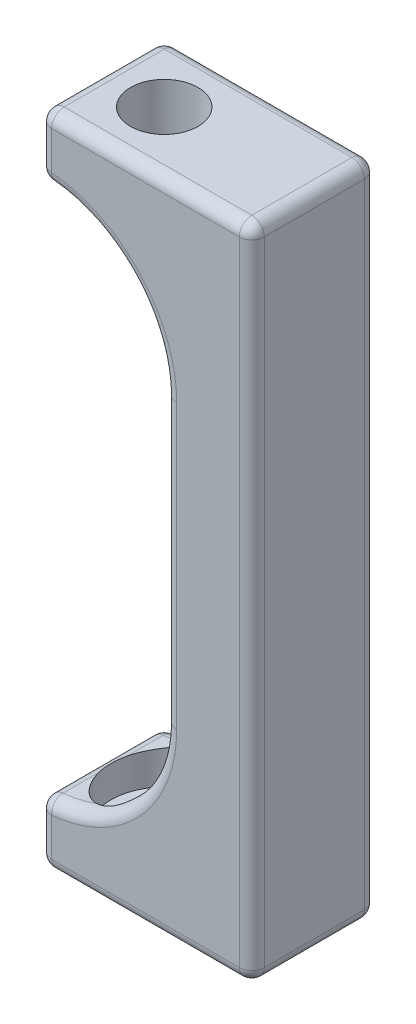
SolidWorks part; units mm, degrees
ref_plane "Front Plane" through (0, 0, 0) normal (0, 0, 1) x (1, 0, 0)
ref_plane "Top Plane" through (0, 0, 0) normal (0, 1, 0) x (1, 0, 0)
ref_plane "Right Plane" through (0, 0, 0) normal (1, 0, 0) x (0, 0, -1)
sketch "Sketch1" plane through (0, 0, 0) normal (0, 0, 1) x (1, 0, 0)
  line L0 (3.5, 0) -> (-32.6297, 0) construction
  line L1 (-3.5, -26.3) -> (3.5, -26.3)
  line L2 (-3.5, -26.3) -> (-3.5, 26.3)
  line L3 (-3.5, 26.3) -> (3.5, 26.3)
  line L4 (3.5, -26.3) -> (3.5, 26.3)
  line L5 (-3.5, -26.3) -> (3.5, 26.3) construction
  line L6 (-3.5, 26.3) -> (3.5, -26.3) construction
  line L7 (-3.5, 21.3) -> (-13.5, 21.3)
  line L8 (-3.5, -26.3) -> (-13.5, -26.3)
  line L9 (-3.5, -26.3) -> (-3.5, -21.3)
  line L10 (-3.5, -21.3) -> (-13.5, -21.3)
  line L11 (-13.5, -26.3) -> (-13.5, -21.3)
  line L12 (-13.5, 26.3) -> (-13.5, 21.3)
  line L13 (-3.5, 26.3) -> (-13.5, 26.3)
  point P0 (0, 0)
  dimension "D1" = 52.6
  dimension "D2" = 7
  dimension "D3" = 10
  dimension "D4" = 5
extrude "Boss-Extrude1" add sketch "Sketch1" along normal blind 10 contours L2 L13 L12 L7 | L1 L4 L3 L2 | L11 L8 L2 L10 region at (0, 0, 0) region at (-8.5, -23.8, 0) region at (-8.5, 23.8, 0)
sketch "Sketch2" plane through (0, -21.3, 0) normal (0, 1, 0) x (1, 0, 0)
  line L0 (-3.5, 0) -> (-3.5, -10)
  line L1 (3.5, -10) -> (-13.5, -10) construction
  line L2 (-8.5, 0) -> (-8.5, -10) construction
  line L3 (-3.5, -10) -> (-13.5, -10)
  line L4 (-3.5, -10) -> (-3.5, 0)
  line L5 (-3.5, 0) -> (-13.5, 0)
  line L6 (-13.5, -10) -> (-13.5, 0)
  line L7 (-3.5, -5) -> (-13.5, -5) construction
  circle A0 centre (-8.5, -5) radius 4.25
  circle A1 centre (-8.5, -5) radius 2.7
  dimension "D1" = 8.5
  dimension "D2" = 5.4
extrude "Cut-Extrude1" cut sketch "Sketch2" against normal through all both and the other way through all contours A1 region at (-8.5, -21.3, 5)
extrude "Cut-Extrude2" cut sketch "Sketch2<3>" against normal blind 2.5 and the other way blind 40 contours A0 A1 region at (-12.6298, -21.3, 5)
sketch "Sketch2<3>" plane through (0, -21.3, 0) normal (0, 1, 0) x (1, 0, 0) same geometry as "Sketch2"
fillet "Fillet1" radius 10 2 edges at (-3.5, -21.3, 5) (-3.5, 21.3, 5)
fillet "Fillet2" radius 1 22 edges at (-13.5, -21.3, 5) (-13.5, -26.3, 5) (-13.5, 26.3, 5) (-13.5, 21.3, 5) (3.5, -26.3, 5) (3.5, 26.3, 5) (-6.4289, -18.3711, 0) (-13.5, -23.8, 0) (-5, -26.3, 0) (3.5, 0, 0) (-5, 26.3, 0) (-13.5, 23.8, 0) (-6.4289, 18.3711, 0) (-3.5, 0, 0) (-5, 26.3, 10) (3.5, 0, 10) (-5, -26.3, 10) (-13.5, -23.8, 10) (-6.4289, -18.3711, 10) (-3.5, 0, 10) (-6.4289, 18.3711, 10) (-13.5, 23.8, 10)
